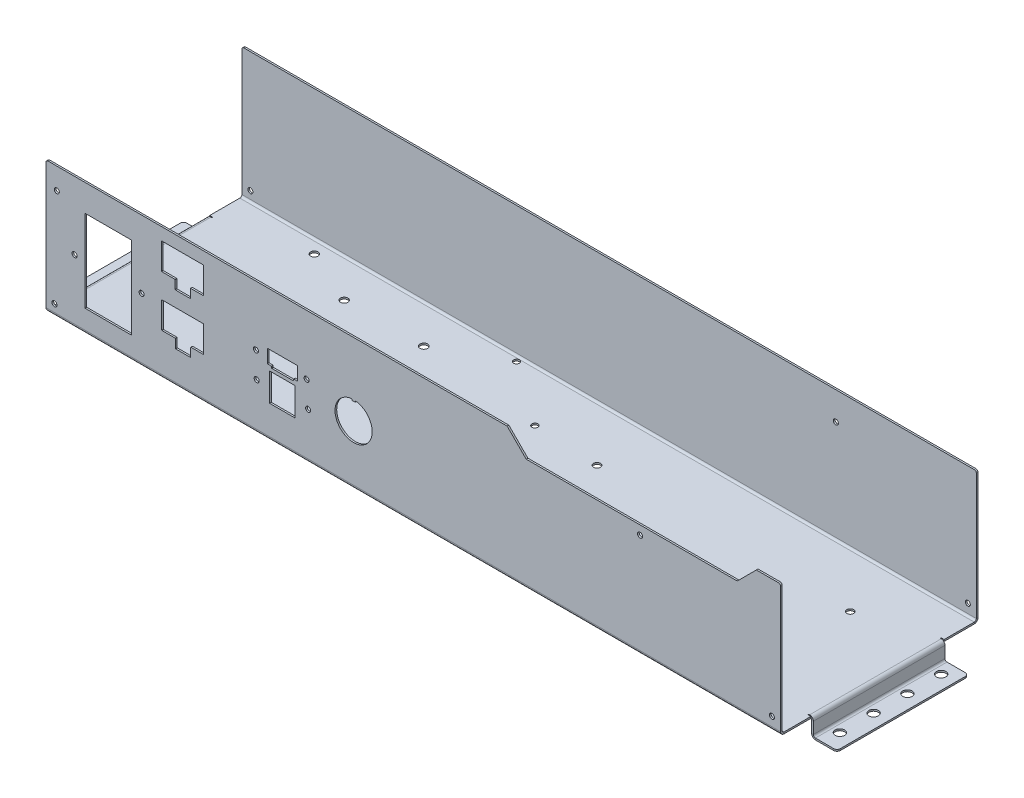
SolidWorks part; units mm, degrees
note: The reader was unsure of these and kept them because the rebuilt part matched: flange length of "Edge-Flange1", "Edge-Flange2", "Edge-Flange3", "Edge-Flange4".
material "1023 Carbon Steel Sheet (SS)"
ref_plane "Front Plane" through (0, 0, 0) normal (0, 0, 1) x (1, 0, 0)
ref_plane "Top Plane" through (0, 0, 0) normal (0, 1, 0) x (1, 0, 0)
ref_plane "Right Plane" through (0, 0, 0) normal (1, 0, 0) x (0, 0, -1)
sketch "Sketch1" plane through (0, 0, 0) normal (0, 1, 0) x (1, 0, 0)
  line L1 (-217.5, -57.5) -> (217.5, -57.5)
  line L2 (-217.5, -57.5) -> (-217.5, 57.5)
  line L3 (-217.5, 57.5) -> (217.5, 57.5)
  line L4 (217.5, -57.5) -> (217.5, 57.5)
  line L5 (-217.5, -57.5) -> (217.5, 57.5) construction
  line L6 (-217.5, 57.5) -> (217.5, -57.5) construction
  point P0 (0, 0)
base flange "Base-Flange1" sketch "Sketch1" thickness 1 reverse thickness direction no parameters "D1"=1.214
edge flange "Edge-Flange1" sketch "Sketch8" flange angle 90 flange length 78 flange position material outside bend radius 1.214 thickness 1 relief rectangular parameters "D6"=10
sketch "Sketch8" plane through (0, 0, 57.5) normal (0, 0, 1) x (1, 0, 0)
  line L0 (-217.5, 0) -> (217.5, 0) construction
  line L1 (-217.5, 0) -> (217.5, 0)
  line L2 (-217.5, 0) -> (-217.5, 77)
  line L3 (-217.5, 77) -> (217.5, 77)
  line L4 (217.5, 77) -> (217.5, 0)
bend "EdgeBend1" bend radius 1.214 bend angle 90 parameters "D5"=1
edge flange "Edge-Flange2" sketch "Sketch11" flange angle 90 flange length 78 flange position material outside bend radius 1.214 thickness 1 relief rectangular parameters "D6"=10
sketch "Sketch11" plane through (0, 0, -57.5) normal (0, 0, -1) x (-1, 0, 0)
  line L0 (-217.5, 0) -> (217.5, 0) construction
  line L1 (-217.5, 0) -> (217.5, 0)
  line L2 (-217.5, 0) -> (-217.5, 77)
  line L3 (-217.5, 77) -> (217.5, 77)
  line L4 (217.5, 77) -> (217.5, 0)
bend "EdgeBend2" bend radius 1.214 bend angle 90 parameters "D5"=2
edge flange "Edge-Flange3" sketch "Sketch35" flange angle 90 flange length 10.214 flange position material outside bend radius 1.214 thickness 1 relief rectangular parameters "D6"=10
bend "EdgeBend5" bend radius 1.214 bend angle 90 parameters "D5"=3
sketch "Sketch35" plane through (217.5, -1, 0) normal (1, 0, 0) x (0, 0, 1)
  line L5 (56.286, 0) -> (-56.286, 0) construction
  line L7 (-37.9399, 0) -> (39.9995, 0)
  line L8 (-37.9399, 0) -> (-37.9399, 9.214)
  line L9 (-37.9399, 9.214) -> (39.9995, 9.214)
  line L10 (39.9995, 0) -> (39.9995, 9.214)
  line L11 (-37.9399, 0) -> (39.9995, 9.214) construction
  line L12 (-37.9399, 9.214) -> (39.9995, 0) construction
  point P8 (1.0298, 4.607)
edge flange "Edge-Flange4" sketch "Sketch39" flange angle 90 flange length 15 flange position material outside bend radius 1.214 thickness 1 relief rectangular parameters "D6"=10
bend "EdgeBend6" bend radius 1.214 bend angle 90 parameters "D5"=4
sketch "Sketch39" plane through (218.5, -10.214, 0) normal (0, -1, 0) x (0, 0, -1)
  line L0 (-39.9995, 0) -> (37.9399, 0) construction
  line L1 (-39.9995, 0) -> (37.9399, 0)
  line L2 (-39.9995, 0) -> (-39.9995, 14)
  line L3 (-39.9995, 14) -> (37.9399, 14)
  line L4 (37.9399, 14) -> (37.9399, 0)
mirror "Mirror1" about plane through (0, 0, 0) normal (1, 0, 0) of "Edge-Flange3", "Edge-Flange4"
bend "MirrorBend3" bend radius 1.214 bend angle 90 parameters "D5"=9
bend "MirrorBend4" bend radius 1.214 bend angle 90 parameters "D5"=12
fillet "Fillet1" radius 2 4 edges at (-232.5, -10.714, 39.9995) (-232.5, -10.714, -37.9399) (232.5, -10.714, -37.9399) (232.5, -10.714, 39.9995)
fillet "Fillet2" radius 1.21 4 edges at (-217.5, 77, 58) (-217.5, 77, -58) (217.5, 77, -58) (217.5, 77, 58)
sketch "Sketch18" plane through (0, 0, 58.5) normal (0, 0, 1) x (1, 0, 0)
  line L1 (216.29, 77) -> (-216.29, 77) construction
  line L4 (191.9151, 65.6863) -> (203.2288, 77)
  line L5 (191.9151, 65.6863) -> (66.9151, 65.6863)
  line L6 (66.9151, 65.6863) -> (55.6014, 77)
  line L7 (55.6014, 77) -> (203.2288, 77)
extrude "Cut-Extrude1" cut sketch "Sketch18" against normal blind 10 normal cut yes
sketch "Sketch23" plane through (0, 0, 58.5) normal (0, 0, 1) x (1, 0, 0)
  line L1 (-92.7472, 26.6535) -> (-77.4972, 26.6535) construction
  line L2 (-85.0472, 18.3535) -> (-69.9472, 18.3535)
  line L3 (-85.0472, 18.3535) -> (-85.0472, 34.9535)
  line L4 (-85.0472, 34.9535) -> (-69.9472, 34.9535)
  line L5 (-69.9472, 18.3535) -> (-69.9472, 34.9535)
  line L6 (-85.0472, 18.3535) -> (-69.9472, 34.9535) construction
  line L7 (-85.0472, 34.9535) -> (-69.9472, 18.3535) construction
  line L8 (-77.4972, 26.6535) -> (-62.2472, 26.6535) construction
  circle A1 centre (-92.7472, 26.6535) radius 1.5
  circle A2 centre (-62.2472, 26.6535) radius 1.5
  point P6 (-77.4972, 26.6535)
extrude "Cut-Extrude3" cut sketch "Sketch23" against normal blind 10 normal cut yes
sketch "Sketch24" plane through (0, 0, 58.5) normal (0, 0, 1) x (1, 0, 0)
  line L5 (-36.1212, 44.2123) -> (-34.5212, 44.2123)
  line L6 (-36.3212, 44.4123) -> (-36.3212, 44.8271)
  line L8 (-34.3212, 44.4123) -> (-34.3212, 44.8271)
  arc A0 (-36.5434, 45.0259) -> (-34.0989, 45.0259) centre (-35.3212, 34.094) ccw
  arc A2 (-34.0989, 45.0259) -> (-34.3212, 44.8271) centre (-34.1212, 44.8271) ccw
  arc A3 (-36.5434, 45.0259) -> (-36.3212, 44.8271) centre (-36.5212, 44.8271) cw
  arc A4 (-34.5212, 44.2123) -> (-34.3212, 44.4123) centre (-34.5212, 44.4123) ccw
  arc A5 (-36.3212, 44.4123) -> (-36.1212, 44.2123) centre (-36.1212, 44.4123) ccw
  dimension "D1" = 0.2
extrude "Cut-Extrude4" cut sketch "Sketch24" against normal blind 10 normal cut yes
sketch "Sketch25" plane through (0, 0, 58.5) normal (0, 0, 1) x (1, 0, 0)
  line L1 (-78.1609, 41.649) -> (-93.1609, 41.649) construction
  line L2 (-86.2439, 45.9317) -> (-68.7439, 45.9317)
  line L3 (-86.4439, 45.7317) -> (-86.4439, 38.1317)
  line L4 (-83.7275, 36.9025) -> (-71.1715, 36.9025)
  line L5 (-68.5439, 45.7317) -> (-68.5439, 38.1317)
  line L6 (-86.4439, 45.9317) -> (-69.8778, 37.3662) construction
  line L7 (-85.0353, 37.3556) -> (-68.5439, 45.9317) construction
  line L8 (-78.1609, 41.649) -> (-63.1609, 41.649) construction
  line L12 (-86.2439, 37.9317) -> (-84.1275, 37.9317)
  line L13 (-83.9275, 37.1025) -> (-83.9275, 37.7317)
  line L14 (-85.0353, 37.3556) -> (-83.9275, 37.9317) construction
  line L15 (-86.4439, 37.9317) -> (-83.9275, 36.9025) construction
  line L18 (-68.7439, 37.9317) -> (-70.7715, 37.9317)
  line L19 (-70.9715, 37.1025) -> (-70.9715, 37.7317)
  line L20 (-69.8778, 37.3662) -> (-70.9715, 37.9317) construction
  line L21 (-68.5439, 37.9317) -> (-70.9715, 36.9025) construction
  circle A0 centre (-93.1609, 41.649) radius 1.5
  circle A1 centre (-63.1609, 41.649) radius 1.5
  arc A2 (-86.4439, 45.7317) -> (-86.2439, 45.9317) centre (-86.2439, 45.7317) cw
  arc A3 (-68.7439, 45.9317) -> (-68.5439, 45.7317) centre (-68.7439, 45.7317) cw
  arc A4 (-86.2439, 37.9317) -> (-86.4439, 38.1317) centre (-86.2439, 38.1317) cw
  arc A5 (-68.5439, 38.1317) -> (-68.7439, 37.9317) centre (-68.7439, 38.1317) cw
  arc A6 (-70.9715, 37.7317) -> (-70.7715, 37.9317) centre (-70.7715, 37.7317) cw
  arc A7 (-70.9715, 37.1025) -> (-71.1715, 36.9025) centre (-71.1715, 37.1025) cw
  arc A8 (-83.9275, 37.1025) -> (-83.7275, 36.9025) centre (-83.7275, 37.1025) ccw
  arc A9 (-84.1275, 37.9317) -> (-83.9275, 37.7317) centre (-84.1275, 37.7317) cw
  point P6 (-77.4681, 41.2908)
  point P15 (-85.0353, 37.3556)
  point P19 (-69.8778, 37.3662)
  dimension "D1" = 0.2
extrude "Cut-Extrude5" cut sketch "Sketch25" against normal blind 10 normal cut yes
sketch "Sketch26" plane through (0, 0, 58.5) normal (0, 0, 1) x (1, 0, 0)
  line L2 (-196.1304, 12.4029) -> (-166.9783, 12.4029) construction
  line L3 (-180.7283, 36.8029) -> (-200.5783, 36.8029) construction
  line L4 (-166.9783, 12.6032) -> (-166.9783, 60.9529)
  line L5 (-167.1787, 12.4032) -> (-194.2787, 12.4526)
  line L6 (-194.4783, 12.6526) -> (-194.4783, 60.9529)
  line L7 (-167.1783, 61.1529) -> (-194.2783, 61.1529)
  line L8 (-166.9783, 12.4029) -> (-194.4783, 61.1529) construction
  line L9 (-194.4783, 12.453) -> (-166.9783, 61.1529) construction
  line L10 (-180.7283, 36.8029) -> (-160.8783, 36.7779) construction
  line L13 (-148.7511, 39.548) -> (-124.3511, 39.548)
  line L16 (-148.9511, 69.6821) -> (-124.5511, 69.6821)
  line L18 (-141.2011, 53.9321) -> (-148.9511, 53.9321)
  line L19 (-140.8011, 48.5821) -> (-132.2011, 48.5821)
  line L25 (-141.0011, 23.798) -> (-148.7511, 23.798)
  line L26 (-149.1511, 69.4821) -> (-149.1511, 54.1321)
  line L32 (-132.0011, 53.7321) -> (-132.0011, 48.7821)
  line L35 (-141.0011, 48.7821) -> (-141.0011, 53.7321)
  line L36 (-131.8011, 53.9321) -> (-124.5511, 53.9321)
  line L37 (-124.3511, 54.1321) -> (-124.3511, 69.4821)
  line L38 (-140.6011, 18.448) -> (-132.0011, 18.448)
  line L39 (-148.9511, 39.348) -> (-148.9511, 23.998)
  line L40 (-131.8011, 23.598) -> (-131.8011, 18.648)
  line L41 (-140.8011, 18.648) -> (-140.8011, 23.598)
  line L42 (-131.6011, 23.798) -> (-124.3511, 23.798)
  line L43 (-124.1511, 23.998) -> (-124.1511, 39.348)
  circle A0 centre (-200.5783, 36.8029) radius 1.5
  circle A1 centre (-160.8783, 36.7779) radius 1.5
  arc A2 (-148.9511, 53.9321) -> (-149.1511, 54.1321) centre (-148.9511, 54.1321) cw
  arc A3 (-141.2011, 53.9321) -> (-141.0011, 53.7321) centre (-141.2011, 53.7321) cw
  arc A4 (-140.8011, 48.5821) -> (-141.0011, 48.7821) centre (-140.8011, 48.7821) cw
  arc A5 (-132.0011, 48.7821) -> (-132.2011, 48.5821) centre (-132.2011, 48.7821) cw
  arc A6 (-132.0011, 53.7321) -> (-131.8011, 53.9321) centre (-131.8011, 53.7321) cw
  arc A7 (-124.5511, 53.9321) -> (-124.3511, 54.1321) centre (-124.5511, 54.1321) ccw
  arc A8 (-124.5511, 69.6821) -> (-124.3511, 69.4821) centre (-124.5511, 69.4821) cw
  arc A9 (-149.1511, 69.4821) -> (-148.9511, 69.6821) centre (-148.9511, 69.4821) cw
  arc A10 (-148.7511, 23.798) -> (-148.9511, 23.998) centre (-148.7511, 23.998) cw
  arc A11 (-141.0011, 23.798) -> (-140.8011, 23.598) centre (-141.0011, 23.598) cw
  arc A12 (-140.6011, 18.448) -> (-140.8011, 18.648) centre (-140.6011, 18.648) cw
  arc A13 (-131.8011, 18.648) -> (-132.0011, 18.448) centre (-132.0011, 18.648) cw
  arc A14 (-131.8011, 23.598) -> (-131.6011, 23.798) centre (-131.6011, 23.598) cw
  arc A15 (-124.3511, 23.798) -> (-124.1511, 23.998) centre (-124.3511, 23.998) ccw
  arc A16 (-124.3511, 39.548) -> (-124.1511, 39.348) centre (-124.3511, 39.348) cw
  arc A17 (-148.9511, 39.348) -> (-148.7511, 39.548) centre (-148.7511, 39.348) cw
  arc A18 (-166.9783, 60.9529) -> (-167.1783, 61.1529) centre (-167.1783, 60.9529) ccw
  arc A19 (-167.1787, 12.4032) -> (-166.9783, 12.6032) centre (-167.1783, 12.6032) ccw
  arc A20 (-194.2787, 12.4526) -> (-194.4783, 12.6526) centre (-194.2783, 12.6526) cw
  arc A21 (-194.4783, 60.9529) -> (-194.2783, 61.1529) centre (-194.2783, 60.9529) cw
  point P8 (-180.7354, 36.7904)
  point P25 (-136.5011, 51.2571)
  point P51 (-103.5793, 43.7286)
  dimension "D1" = 0.2
  dimension "D3" = 0.2
extrude "Cut-Extrude6" cut sketch "Sketch26" against normal blind 10 normal cut yes
sketch "Sketch28" plane through (0, 0, 58.5) normal (0, 0, 1) x (1, 0, 0)
  line L3 (-66.8168, 56.388) -> (-87.3168, 56.388)
  line L4 (-66.6168, 56.188) -> (-66.6168, 51.088)
  line L6 (-87.5168, 56.188) -> (-87.5168, 51.088)
  line L8 (-75.0865, 50.888) -> (-66.8168, 50.888)
  line L9 (-77.0668, 49.188) -> (-75.0865, 49.188) construction
  line L10 (-77.0668, 49.188) -> (-79.0471, 49.188) construction
  line L12 (-75.0865, 49.188) -> (-79.0471, 49.188)
  line L13 (-75.0865, 49.188) -> (-75.0865, 50.888)
  line L15 (-79.0471, 49.188) -> (-79.0471, 50.888)
  line L16 (-79.0471, 50.888) -> (-87.3168, 50.888)
  arc A0 (-87.3168, 50.888) -> (-87.5168, 51.088) centre (-87.3168, 51.088) cw
  arc A1 (-87.3168, 56.388) -> (-87.5168, 56.188) centre (-87.3168, 56.188) ccw
  arc A2 (-66.8168, 56.388) -> (-66.6168, 56.188) centre (-66.8168, 56.188) cw
  arc A3 (-66.6168, 51.088) -> (-66.8168, 50.888) centre (-66.8168, 51.088) cw
  point P6 (-77.0668, 56.388)
  dimension "D2" = 0.2
sketch "Sketch29" plane through (0, -1, 0) normal (0, -1, 0) x (1, 0, 0)
  line L5 (-216.286, 56.286) -> (-216.286, -56.286) construction
  line L6 (-216.286, 56.286) -> (206.646, 56.286) construction
  line L7 (206.646, 56.286) -> (206.646, -56.286) construction
  line L8 (-216.286, -56.286) -> (206.646, -56.286) construction
  line L9 (-216.286, 56.286) -> (206.646, -56.286) construction
  line L10 (206.646, 56.286) -> (-216.286, -56.286) construction
  circle A0 centre (-166.7317, -2.49) radius 2.2
  circle A1 centre (-166.7317, -49.66) radius 2.2
  circle A2 centre (-134.2117, -34.82) radius 2.2
  circle A3 centre (-87.0417, -34.82) radius 2.2731
  circle A4 centre (-95.9046, 5) radius 1.8481
  circle A5 centre (-37.9046, 5) radius 1.85
  circle A6 centre (-37.9046, 54) radius 1.85
  circle A9 centre (-51.698, -54.38) radius 1.75
  circle A11 centre (-13.438, -27.02) radius 1.786
  circle A12 centre (25.36, -25) radius 2.0474
  circle A13 centre (25.36, 25) radius 2
  circle A14 centre (175.36, 25) radius 2
  circle A15 centre (175.36, -25) radius 2
  point P52 (-4.213, -0.607)
  point P57 (-4.82, 0)
extrude "Cut-Extrude8" cut sketch "Sketch29" against normal blind 10 normal cut yes
sketch "Sketch30" plane through (0, 0, 58.5) normal (0, 0, 1) x (1, 0, 0)
  line L0 (-212.3259, 76.6451) -> (212.6797, 76.6451) construction
  line L1 (-212.3259, 76.6451) -> (-212.3259, 1.2135) construction
  line L2 (-212.3259, 1.2135) -> (212.6797, 1.2135) construction
  line L3 (212.6797, 76.6451) -> (212.6797, 1.2135) construction
  line L4 (-212.3259, 76.6451) -> (212.6797, 1.2135) construction
  line L5 (-212.3259, 1.2135) -> (212.6797, 76.6451) construction
  circle A0 centre (212.4742, 6.5618) radius 1.5
  circle A1 centre (134.3351, 60.4505) radius 1.5
  circle A2 centre (-212.4748, 5.6818) radius 1.5
  point P4 (0.1769, 38.9293)
extrude "Cut-Extrude9" cut sketch "Sketch30" against normal blind 10 normal cut yes
mirror "Mirror2" about plane through (0, 0, 0) normal (0, 0, 1) of "Cut-Extrude9"
sketch "Sketch31" plane through (0, -10.214, 0) normal (0, 1, 0) x (1, 0, 0)
  line L0 (-232.5, 0) -> (-224.18, 0) construction
  line L2 (-224.18, 0) -> (-224.18, 10) construction
  circle A0 centre (-224.18, 10) radius 2.8
  circle A1 centre (-224.18, 30) radius 2.8
  dimension "D1" = 2
extrude "Cut-Extrude10" cut sketch "Sketch31" against normal blind 10 normal cut yes
mirror "Mirror3" about plane through (0, 0, 0) normal (0, 0, 1) of "Cut-Extrude10"
mirror "Mirror4" about plane through (0, 0, 0) normal (1, 0, 0) of "Mirror3", "Cut-Extrude10"
sketch "Sketch37" plane through (0, 0, 58.5) normal (0, 0, 1) x (1, 0, 0)
  line L0 (-217.1456, 76.6456) -> (-217.1456, 64.3256) construction
  line L1 (-217.1456, 64.3256) -> (-211.1156, 64.3256) construction
  arc A0 (-216.29, 77) -> (-217.5, 75.79) centre (-216.29, 75.79) ccw construction
  circle A1 centre (-211.1156, 64.3256) radius 1.5
extrude "Cut-Extrude12" cut sketch "Sketch37" against normal blind 10 normal cut yes
sketch "Bend-Lines1" [suppressed] plane through (0, 0, 0) normal (0, 1, 0) x (1, 0, 0)
sketch "Bounding-Box1" [suppressed] plane through (0, 0, 0) normal (0, 1, 0) x (1, 0, 0)
sheet metal parameters "Sheet-Metal1" thickness 1 parameters "D1"=1.214
flat pattern "Flat-Pattern1" [suppressed]
sketch "Bend-Lines2" plane through (0, 0, 0) normal (0, 1, 0) x (1, 0, 0)
sketch3d "Bounding-Box2" [suppressed]
  line L0 (-212.68, 57.5, 0) -> (212.68, 57.5, 0) construction
  line L1 (-212.68, -57.5, 0) -> (212.68, -57.5, 0) construction
  line L2 (-212.68, 57.5, 0) -> (-212.68, -57.5, 0) construction
  line L3 (212.68, 57.5, 0) -> (212.68, -57.5, 0) construction
sheet metal parameters "Sheet-Metal2" thickness 1 parameters "D1"=1.214
flat pattern "Flat-Pattern1"
sketch "Bend-Lines2" plane through (0, 0, 0) normal (0, 1, 0) x (1, 0, 0)
  line L0 (-212.68, -57.6322) -> (212.68, -57.6322) construction
  line L1 (-212.68, -57.6322) -> (212.68, -57.6322) construction
sketch3d "Bounding-Box2" [suppressed]
  line L0 (212.68, 57.5, 0) -> (-212.68, 57.5, 0) construction
  line L1 (212.68, -134.7643, 0) -> (-212.68, -134.7643, 0) construction
  line L2 (212.68, 57.5, 0) -> (212.68, -134.7643, 0) construction
  line L3 (-212.68, 57.5, 0) -> (-212.68, -134.7643, 0) construction
bend of the flat pattern "Flatten-<EdgeBend1>1"
sheet metal parameters "Sheet-Metal3" thickness 1 parameters "D1"=1.214
flat pattern "Flat-Pattern1"
sketch "Bend-Lines2" plane through (0, 0, 0) normal (0, 1, 0) x (1, 0, 0)
  line L0 (-212.68, -57.6322) -> (212.68, -57.6322) construction
  line L1 (-212.68, -57.6322) -> (212.68, -57.6322) construction
  line L2 (212.68, 57.6322) -> (-212.68, 57.6322) construction
  line L3 (212.68, 57.6322) -> (-212.68, 57.6322) construction
sketch3d "Bounding-Box2" [suppressed]
  line L0 (212.68, 134.7643, 0) -> (-212.68, 134.7643, 0) construction
  line L1 (212.68, -134.7643, 0) -> (-212.68, -134.7643, 0) construction
  line L2 (212.68, 134.7643, 0) -> (212.68, -134.7643, 0) construction
  line L3 (-212.68, 134.7643, 0) -> (-212.68, -134.7643, 0) construction
bend of the flat pattern "Flatten-<EdgeBend1>1"
bend of the flat pattern "Flatten-<EdgeBend2>1"
sheet metal parameters "Sheet-Metal4" thickness 1 parameters "D1"=1.214
flat pattern "Flat-Pattern1" [suppressed]
sketch "Bend-Lines2" plane through (0, -1, 0) normal (0, -1, 0) x (-1, 0, 0)
  line L0 (217.5, -57.6322) -> (-217.5, -57.6322) construction
  line L1 (217.5, -57.6322) -> (-217.5, -57.6322) construction
  line L2 (-217.5, 57.6322) -> (217.5, 57.6322) construction
  line L3 (-217.5, 57.6322) -> (217.5, 57.6322) construction
  line L6 (-217.6322, -39.9995) -> (-217.6322, 37.9399) construction
  line L7 (-217.6322, -39.9995) -> (-217.6322, 37.9399) construction
  point P4 (217.6322, -45)
  point P5 (217.6322, 22.5)
sketch3d "Bounding-Box2" [suppressed]
  line L0 (-226.9783, 134.7643, 0) -> (217.5, 134.7643, 0) construction
  line L1 (-226.9783, -134.7643, 0) -> (217.5, -134.7643, 0) construction
  line L2 (-226.9783, 134.7643, 0) -> (-226.9783, -134.7643, 0) construction
  line L3 (217.5, 134.7643, 0) -> (217.5, -134.7643, 0) construction
bend of the flat pattern "Flatten-<EdgeBend1>1"
bend of the flat pattern "Flatten-<EdgeBend2>1"
bend of the flat pattern "Flatten-<EdgeBend5>1"
sketch "Sketch28-2" plane through (0, -1, 57.7643) normal (0, -1, 0) x (1, 0, 0)
  line L3 (-66.8168, 56.388) -> (-87.3168, 56.388)
  line L4 (-66.6168, 56.188) -> (-66.6168, 51.088)
  line L6 (-87.5168, 56.188) -> (-87.5168, 51.088)
  line L8 (-75.0865, 50.888) -> (-66.8168, 50.888)
  line L9 (-77.0668, 49.188) -> (-75.0865, 49.188) construction
  line L10 (-77.0668, 49.188) -> (-79.0471, 49.188) construction
  line L12 (-75.0865, 49.188) -> (-79.0471, 49.188)
  line L13 (-75.0865, 49.188) -> (-75.0865, 50.888)
  line L15 (-79.0471, 49.188) -> (-79.0471, 50.888)
  line L16 (-79.0471, 50.888) -> (-87.3168, 50.888)
  arc A0 (-87.3168, 50.888) -> (-87.5168, 51.088) centre (-87.3168, 51.088) cw
  arc A1 (-87.3168, 56.388) -> (-87.5168, 56.188) centre (-87.3168, 56.188) ccw
  arc A2 (-66.8168, 56.388) -> (-66.6168, 56.188) centre (-66.8168, 56.188) cw
  arc A3 (-66.6168, 51.088) -> (-66.8168, 50.888) centre (-66.8168, 51.088) cw
  dimension "D2" = 0.2
sheet metal parameters "Sheet-Metal5" thickness 1 parameters "D1"=1.214
flat pattern "Flat-Pattern1" [suppressed]
sketch "Bend-Lines2" plane through (0, 0, 0) normal (0, 1, 0) x (1, 0, 0)
  line L0 (-212.68, -57.6322) -> (212.68, -57.6322) construction
  line L1 (-212.68, -57.6322) -> (212.68, -57.6322) construction
  line L2 (212.68, 57.6322) -> (-212.68, 57.6322) construction
  line L3 (212.68, 57.6322) -> (-212.68, 57.6322) construction
  line L4 (212.8122, -56.286) -> (212.8122, 56.286) construction
  line L5 (212.8122, -56.286) -> (212.8122, 56.286) construction
  line L6 (222.2905, -56.286) -> (222.2905, 56.286) construction
  line L7 (222.2905, -56.286) -> (222.2905, 56.286) construction
sketch3d "Bounding-Box2" [suppressed]
  line L0 (241.4227, 134.7643, 0) -> (-212.68, 134.7643, 0) construction
  line L1 (241.4227, -134.7643, 0) -> (-212.68, -134.7643, 0) construction
  line L2 (241.4227, 134.7643, 0) -> (241.4227, -134.7643, 0) construction
  line L3 (-212.68, 134.7643, 0) -> (-212.68, -134.7643, 0) construction
bend of the flat pattern "Flatten-<EdgeBend1>1"
bend of the flat pattern "Flatten-<EdgeBend2>1"
bend of the flat pattern "Flatten-<EdgeBend5>2"
bend of the flat pattern "Flatten-<EdgeBend6>1"
sheet metal parameters "Sheet-Metal6" thickness 1 parameters "D1"=1.214
flat pattern "Flat-Pattern1" [suppressed]
sketch "Bend-Lines2" plane through (0, 0, 0) normal (0, 1, 0) x (1, 0, 0)
  line L0 (-212.68, -57.6322) -> (212.68, -57.6322) construction
  line L1 (-212.68, -57.6322) -> (212.68, -57.6322) construction
  line L2 (212.68, 57.6322) -> (-212.68, 57.6322) construction
  line L3 (212.68, 57.6322) -> (-212.68, 57.6322) construction
  line L4 (212.8122, -56.286) -> (212.8122, 56.286) construction
  line L5 (212.8122, -56.286) -> (212.8122, 56.286) construction
  line L6 (222.2905, -56.286) -> (222.2905, 56.286) construction
  line L7 (222.2905, -56.286) -> (222.2905, 56.286) construction
  line L8 (-222.2905, 56.286) -> (-222.2905, -56.286) construction
  line L9 (-212.8122, 56.286) -> (-212.8122, -56.286) construction
  line L10 (-222.2905, 56.286) -> (-222.2905, -56.286) construction
  line L11 (-212.8122, 56.286) -> (-212.8122, -56.286) construction
sketch3d "Bounding-Box2" [suppressed]
  line L0 (241.4227, 134.7643, 0) -> (-241.4227, 134.7643, 0) construction
  line L1 (241.4227, -134.7643, 0) -> (-241.4227, -134.7643, 0) construction
  line L2 (241.4227, 134.7643, 0) -> (241.4227, -134.7643, 0) construction
  line L3 (-241.4227, 134.7643, 0) -> (-241.4227, -134.7643, 0) construction
bend of the flat pattern "Flatten-<EdgeBend1>1"
bend of the flat pattern "Flatten-<EdgeBend2>1"
bend of the flat pattern "Flatten-<EdgeBend5>3"
bend of the flat pattern "Flatten-<MirrorBend3>1"
bend of the flat pattern "Flatten-<EdgeBend6>2"
bend of the flat pattern "Flatten-<MirrorBend4>1"
sheet metal parameters "Sheet-Metal7" thickness 1 parameters "D1"=1.214
flat pattern "Flat-Pattern1" [suppressed]
sketch "Bend-Lines2" plane through (0, 0, 0) normal (0, 1, 0) x (1, 0, 0)
  line L0 (-212.68, -57.6322) -> (212.68, -57.6322) construction
  line L1 (-212.68, -57.6322) -> (212.68, -57.6322) construction
  line L2 (212.68, 57.6322) -> (-212.68, 57.6322) construction
  line L3 (212.68, 57.6322) -> (-212.68, 57.6322) construction
  line L4 (212.8122, -56.286) -> (212.8122, 56.286) construction
  line L5 (212.8122, -56.286) -> (212.8122, 56.286) construction
  line L6 (222.2905, -56.286) -> (222.2905, 56.286) construction
  line L7 (222.2905, -56.286) -> (222.2905, 56.286) construction
  line L8 (-222.2905, 56.286) -> (-222.2905, -56.286) construction
  line L9 (-212.8122, 56.286) -> (-212.8122, -56.286) construction
  line L10 (-222.2905, 56.286) -> (-222.2905, -56.286) construction
  line L11 (-212.8122, 56.286) -> (-212.8122, -56.286) construction
sketch3d "Bounding-Box2" [suppressed]
  line L0 (241.4227, 134.7643, 0) -> (-241.4227, 134.7643, 0) construction
  line L1 (241.4227, -134.7643, 0) -> (-241.4227, -134.7643, 0) construction
  line L2 (241.4227, 134.7643, 0) -> (241.4227, -134.7643, 0) construction
  line L3 (-241.4227, 134.7643, 0) -> (-241.4227, -134.7643, 0) construction
bend of the flat pattern "Flatten-<EdgeBend1>1"
bend of the flat pattern "Flatten-<EdgeBend2>1"
bend of the flat pattern "Flatten-<EdgeBend5>4"
bend of the flat pattern "Flatten-<MirrorBend3>2"
bend of the flat pattern "Flatten-<EdgeBend6>3"
bend of the flat pattern "Flatten-<MirrorBend4>2"
sheet metal parameters "Sheet-Metal9" thickness 1 parameters "D1"=1.214
flat pattern "Flat-Pattern1" [suppressed]
sketch "Bend-Lines2" plane through (0, 0, 0) normal (0, 1, 0) x (1, 0, 0)
  line L0 (-212.68, -57.6322) -> (212.68, -57.6322) construction
  line L1 (-212.68, -57.6322) -> (212.68, -57.6322) construction
  line L2 (212.68, 57.6322) -> (-212.68, 57.6322) construction
  line L3 (212.68, 57.6322) -> (-212.68, 57.6322) construction
  line L4 (212.8122, -56.286) -> (212.8122, 56.286) construction
  line L5 (212.8122, -56.286) -> (212.8122, 56.286) construction
  line L6 (222.2905, -56.286) -> (222.2905, 56.286) construction
  line L7 (222.2905, -56.286) -> (222.2905, 56.286) construction
  line L8 (-222.2905, 56.286) -> (-222.2905, -56.286) construction
  line L9 (-212.8122, 56.286) -> (-212.8122, -56.286) construction
  line L10 (-222.2905, 56.286) -> (-222.2905, -56.286) construction
  line L11 (-212.8122, 56.286) -> (-212.8122, -56.286) construction
sketch3d "Bounding-Box2" [suppressed]
  line L0 (241.4227, 134.7643, 0) -> (-241.4227, 134.7643, 0) construction
  line L1 (241.4227, -134.7643, 0) -> (-241.4227, -134.7643, 0) construction
  line L2 (241.4227, 134.7643, 0) -> (241.4227, -134.7643, 0) construction
  line L3 (-241.4227, 134.7643, 0) -> (-241.4227, -134.7643, 0) construction
bend of the flat pattern "Flatten-<EdgeBend1>1"
bend of the flat pattern "Flatten-<EdgeBend2>1"
bend of the flat pattern "Flatten-<EdgeBend5>5"
bend of the flat pattern "Flatten-<MirrorBend3>3"
bend of the flat pattern "Flatten-<EdgeBend6>4"
bend of the flat pattern "Flatten-<MirrorBend4>3"
sheet metal parameters "Sheet-Metal10" thickness 1 parameters "D1"=1.214
flat pattern "Flat-Pattern1" [suppressed]
sketch "Bend-Lines2" plane through (0, 0, 0) normal (0, 1, 0) x (1, 0, 0)
  line L0 (-212.68, -57.6322) -> (212.68, -57.6322) construction
  line L1 (-212.68, -57.6322) -> (212.68, -57.6322) construction
  line L2 (212.68, 57.6322) -> (-212.68, 57.6322) construction
  line L3 (212.68, 57.6322) -> (-212.68, 57.6322) construction
  line L4 (212.8122, -56.286) -> (212.8122, 56.286) construction
  line L5 (212.8122, -56.286) -> (212.8122, 56.286) construction
  line L6 (222.2905, -56.286) -> (222.2905, 56.286) construction
  line L7 (222.2905, -56.286) -> (222.2905, 56.286) construction
  line L8 (-222.2905, 56.286) -> (-222.2905, -56.286) construction
  line L9 (-212.8122, 56.286) -> (-212.8122, -56.286) construction
  line L10 (-222.2905, 56.286) -> (-222.2905, -56.286) construction
  line L11 (-212.8122, 56.286) -> (-212.8122, -56.286) construction
sketch3d "Bounding-Box2" [suppressed]
  line L0 (241.4227, 134.7643, 0) -> (-241.4227, 134.7643, 0) construction
  line L1 (241.4227, -134.7643, 0) -> (-241.4227, -134.7643, 0) construction
  line L2 (241.4227, 134.7643, 0) -> (241.4227, -134.7643, 0) construction
  line L3 (-241.4227, 134.7643, 0) -> (-241.4227, -134.7643, 0) construction
bend of the flat pattern "Flatten-<EdgeBend1>1"
bend of the flat pattern "Flatten-<EdgeBend2>1"
bend of the flat pattern "Flatten-<EdgeBend5>6"
bend of the flat pattern "Flatten-<MirrorBend3>4"
bend of the flat pattern "Flatten-<EdgeBend6>5"
bend of the flat pattern "Flatten-<MirrorBend4>4"
sheet metal parameters "Sheet-Metal11" thickness 1 parameters "D1"=1.214
flat pattern "Flat-Pattern1" [suppressed]
sketch "Bend-Lines2" plane through (0, 0, 0) normal (0, 1, 0) x (1, 0, 0)
  line L0 (-212.68, -57.6322) -> (212.68, -57.6322) construction
  line L1 (-212.68, -57.6322) -> (212.68, -57.6322) construction
  line L2 (212.68, 57.6322) -> (-212.68, 57.6322) construction
  line L3 (212.68, 57.6322) -> (-212.68, 57.6322) construction
  line L4 (212.8122, -56.286) -> (212.8122, 56.286) construction
  line L5 (212.8122, -56.286) -> (212.8122, 56.286) construction
  line L6 (222.2905, -56.286) -> (222.2905, 56.286) construction
  line L7 (222.2905, -56.286) -> (222.2905, 56.286) construction
  line L8 (-222.2905, 56.286) -> (-222.2905, -56.286) construction
  line L9 (-212.8122, 56.286) -> (-212.8122, -56.286) construction
  line L10 (-222.2905, 56.286) -> (-222.2905, -56.286) construction
  line L11 (-212.8122, 56.286) -> (-212.8122, -56.286) construction
sketch3d "Bounding-Box2" [suppressed]
  line L0 (241.4227, 134.7643, 0) -> (-241.4227, 134.7643, 0) construction
  line L1 (241.4227, -134.7643, 0) -> (-241.4227, -134.7643, 0) construction
  line L2 (241.4227, 134.7643, 0) -> (241.4227, -134.7643, 0) construction
  line L3 (-241.4227, 134.7643, 0) -> (-241.4227, -134.7643, 0) construction
bend of the flat pattern "Flatten-<EdgeBend1>1"
bend of the flat pattern "Flatten-<EdgeBend2>1"
bend of the flat pattern "Flatten-<EdgeBend5>7"
bend of the flat pattern "Flatten-<MirrorBend3>5"
bend of the flat pattern "Flatten-<EdgeBend6>6"
bend of the flat pattern "Flatten-<MirrorBend4>5"
sheet metal parameters "Sheet-Metal12" thickness 1 parameters "D1"=1.214
flat pattern "Flat-Pattern1" [suppressed]
sketch "Bend-Lines2" plane through (0, 0, 0) normal (0, 1, 0) x (1, 0, 0)
  line L0 (-212.68, -57.6322) -> (212.68, -57.6322) construction
  line L1 (-212.68, -57.6322) -> (212.68, -57.6322) construction
  line L2 (212.68, 57.6322) -> (-212.68, 57.6322) construction
  line L3 (212.68, 57.6322) -> (-212.68, 57.6322) construction
  line L4 (212.8122, -56.286) -> (212.8122, 56.286) construction
  line L5 (212.8122, -56.286) -> (212.8122, 56.286) construction
  line L6 (222.2905, -56.286) -> (222.2905, 56.286) construction
  line L7 (222.2905, -56.286) -> (222.2905, 56.286) construction
  line L8 (-222.2905, 56.286) -> (-222.2905, -56.286) construction
  line L9 (-212.8122, 56.286) -> (-212.8122, -56.286) construction
  line L10 (-222.2905, 56.286) -> (-222.2905, -56.286) construction
  line L11 (-212.8122, 56.286) -> (-212.8122, -56.286) construction
sketch3d "Bounding-Box2" [suppressed]
  line L0 (241.4227, 134.7643, 0) -> (-241.4227, 134.7643, 0) construction
  line L1 (241.4227, -134.7643, 0) -> (-241.4227, -134.7643, 0) construction
  line L2 (241.4227, 134.7643, 0) -> (241.4227, -134.7643, 0) construction
  line L3 (-241.4227, 134.7643, 0) -> (-241.4227, -134.7643, 0) construction
bend of the flat pattern "Flatten-<EdgeBend1>1"
bend of the flat pattern "Flatten-<EdgeBend2>1"
bend of the flat pattern "Flatten-<EdgeBend5>8"
bend of the flat pattern "Flatten-<MirrorBend3>6"
bend of the flat pattern "Flatten-<EdgeBend6>7"
bend of the flat pattern "Flatten-<MirrorBend4>6"
sheet metal parameters "Sheet-Metal14" thickness 1 parameters "D1"=1.214
flat pattern "Flat-Pattern1" [suppressed]
sketch "Bend-Lines2" plane through (0, 0, 0) normal (0, 1, 0) x (1, 0, 0)
  line L0 (-212.68, -57.6322) -> (212.68, -57.6322) construction
  line L1 (-212.68, -57.6322) -> (212.68, -57.6322) construction
  line L2 (212.68, 57.6322) -> (-212.68, 57.6322) construction
  line L3 (212.68, 57.6322) -> (-212.68, 57.6322) construction
  line L4 (212.8122, -56.286) -> (212.8122, 56.286) construction
  line L5 (212.8122, -56.286) -> (212.8122, 56.286) construction
  line L6 (222.2905, -56.286) -> (222.2905, 56.286) construction
  line L7 (222.2905, -56.286) -> (222.2905, 56.286) construction
  line L8 (-222.2905, 56.286) -> (-222.2905, -56.286) construction
  line L9 (-212.8122, 56.286) -> (-212.8122, -56.286) construction
  line L10 (-222.2905, 56.286) -> (-222.2905, -56.286) construction
  line L11 (-212.8122, 56.286) -> (-212.8122, -56.286) construction
sketch3d "Bounding-Box2" [suppressed]
  line L0 (241.4227, 134.7643, 0) -> (-241.4227, 134.7643, 0) construction
  line L1 (241.4227, -134.7643, 0) -> (-241.4227, -134.7643, 0) construction
  line L2 (241.4227, 134.7643, 0) -> (241.4227, -134.7643, 0) construction
  line L3 (-241.4227, 134.7643, 0) -> (-241.4227, -134.7643, 0) construction
bend of the flat pattern "Flatten-<EdgeBend1>1"
bend of the flat pattern "Flatten-<EdgeBend2>1"
bend of the flat pattern "Flatten-<EdgeBend5>9"
bend of the flat pattern "Flatten-<MirrorBend3>7"
bend of the flat pattern "Flatten-<EdgeBend6>8"
bend of the flat pattern "Flatten-<MirrorBend4>7"
sheet metal parameters "Sheet-Metal15" thickness 1 parameters "D1"=1.214
flat pattern "Flat-Pattern1" [suppressed]
sketch "Bend-Lines2" plane through (0, 0, 0) normal (0, 1, 0) x (1, 0, 0)
  line L0 (-212.68, -57.6322) -> (212.68, -57.6322) construction
  line L1 (-212.68, -57.6322) -> (212.68, -57.6322) construction
  line L2 (212.68, 57.6322) -> (-212.68, 57.6322) construction
  line L3 (212.68, 57.6322) -> (-212.68, 57.6322) construction
  line L4 (212.8122, -56.286) -> (212.8122, 56.286) construction
  line L5 (212.8122, -56.286) -> (212.8122, 56.286) construction
  line L6 (222.2905, -56.286) -> (222.2905, 56.286) construction
  line L7 (222.2905, -56.286) -> (222.2905, 56.286) construction
  line L8 (-222.2905, 56.286) -> (-222.2905, -56.286) construction
  line L9 (-212.8122, 56.286) -> (-212.8122, -56.286) construction
  line L10 (-222.2905, 56.286) -> (-222.2905, -56.286) construction
  line L11 (-212.8122, 56.286) -> (-212.8122, -56.286) construction
sketch3d "Bounding-Box2" [suppressed]
  line L0 (241.4227, 134.7643, 0) -> (-241.4227, 134.7643, 0) construction
  line L1 (241.4227, -134.7643, 0) -> (-241.4227, -134.7643, 0) construction
  line L2 (241.4227, 134.7643, 0) -> (241.4227, -134.7643, 0) construction
  line L3 (-241.4227, 134.7643, 0) -> (-241.4227, -134.7643, 0) construction
bend of the flat pattern "Flatten-<EdgeBend1>1"
bend of the flat pattern "Flatten-<EdgeBend2>1"
bend of the flat pattern "Flatten-<EdgeBend5>10"
bend of the flat pattern "Flatten-<MirrorBend3>8"
bend of the flat pattern "Flatten-<EdgeBend6>9"
bend of the flat pattern "Flatten-<MirrorBend4>8"
sheet metal parameters "Sheet-Metal16" thickness 1 parameters "D1"=1.214
flat pattern "Flat-Pattern1" [suppressed]
sketch "Bend-Lines2" plane through (0, 0, 0) normal (0, 1, 0) x (1, 0, 0)
  line L0 (-212.68, -57.6322) -> (212.68, -57.6322) construction
  line L1 (-212.68, -57.6322) -> (212.68, -57.6322) construction
  line L2 (212.68, 57.6322) -> (-212.68, 57.6322) construction
  line L3 (212.68, 57.6322) -> (-212.68, 57.6322) construction
  line L4 (212.8122, -56.286) -> (212.8122, 56.286) construction
  line L5 (212.8122, -56.286) -> (212.8122, 56.286) construction
  line L6 (222.2905, -56.286) -> (222.2905, 56.286) construction
  line L7 (222.2905, -56.286) -> (222.2905, 56.286) construction
  line L8 (-222.2905, 56.286) -> (-222.2905, -56.286) construction
  line L9 (-212.8122, 56.286) -> (-212.8122, -56.286) construction
  line L10 (-222.2905, 56.286) -> (-222.2905, -56.286) construction
  line L11 (-212.8122, 56.286) -> (-212.8122, -56.286) construction
sketch3d "Bounding-Box2" [suppressed]
  line L0 (241.4227, 134.7643, 0) -> (-241.4227, 134.7643, 0) construction
  line L1 (241.4227, -134.7643, 0) -> (-241.4227, -134.7643, 0) construction
  line L2 (241.4227, 134.7643, 0) -> (241.4227, -134.7643, 0) construction
  line L3 (-241.4227, 134.7643, 0) -> (-241.4227, -134.7643, 0) construction
bend of the flat pattern "Flatten-<EdgeBend1>1"
bend of the flat pattern "Flatten-<EdgeBend2>1"
bend of the flat pattern "Flatten-<EdgeBend5>11"
bend of the flat pattern "Flatten-<MirrorBend3>9"
bend of the flat pattern "Flatten-<EdgeBend6>10"
bend of the flat pattern "Flatten-<MirrorBend4>9"
sheet metal parameters "Sheet-Metal17" thickness 1 parameters "D1"=1.214
flat pattern "Flat-Pattern1" [suppressed]
sketch "Bend-Lines2" plane through (0, 0, 0) normal (0, 1, 0) x (1, 0, 0)
  line L0 (-212.68, -57.6322) -> (212.68, -57.6322) construction
  line L1 (-212.68, -57.6322) -> (212.68, -57.6322) construction
  line L2 (212.68, 57.6322) -> (-212.68, 57.6322) construction
  line L3 (212.68, 57.6322) -> (-212.68, 57.6322) construction
  line L4 (212.8122, -56.286) -> (212.8122, 56.286) construction
  line L5 (212.8122, -56.286) -> (212.8122, 56.286) construction
  line L6 (222.2905, -56.286) -> (222.2905, 56.286) construction
  line L7 (222.2905, -56.286) -> (222.2905, 56.286) construction
  line L8 (-222.2905, 56.286) -> (-222.2905, -56.286) construction
  line L9 (-212.8122, 56.286) -> (-212.8122, -56.286) construction
  line L10 (-222.2905, 56.286) -> (-222.2905, -56.286) construction
  line L11 (-212.8122, 56.286) -> (-212.8122, -56.286) construction
sketch3d "Bounding-Box2" [suppressed]
  line L0 (241.4227, 134.7643, 0) -> (-241.4227, 134.7643, 0) construction
  line L1 (241.4227, -134.7643, 0) -> (-241.4227, -134.7643, 0) construction
  line L2 (241.4227, 134.7643, 0) -> (241.4227, -134.7643, 0) construction
  line L3 (-241.4227, 134.7643, 0) -> (-241.4227, -134.7643, 0) construction
bend of the flat pattern "Flatten-<EdgeBend1>1"
bend of the flat pattern "Flatten-<EdgeBend2>1"
bend of the flat pattern "Flatten-<EdgeBend5>12"
bend of the flat pattern "Flatten-<MirrorBend3>10"
bend of the flat pattern "Flatten-<EdgeBend6>11"
bend of the flat pattern "Flatten-<MirrorBend4>10"
sheet metal parameters "Sheet-Metal18" thickness 1 parameters "D1"=1.214
flat pattern "Flat-Pattern1" [suppressed]
sketch "Bend-Lines2" plane through (0, 0, 0) normal (0, 1, 0) x (1, 0, 0)
  line L0 (-212.68, -57.6322) -> (212.68, -57.6322) construction
  line L1 (-212.68, -57.6322) -> (212.68, -57.6322) construction
  line L2 (212.68, 57.6322) -> (-212.68, 57.6322) construction
  line L3 (212.68, 57.6322) -> (-212.68, 57.6322) construction
  line L4 (212.8122, -56.286) -> (212.8122, 56.286) construction
  line L5 (212.8122, -56.286) -> (212.8122, 56.286) construction
  line L6 (222.2905, -56.286) -> (222.2905, 56.286) construction
  line L7 (222.2905, -56.286) -> (222.2905, 56.286) construction
  line L8 (-222.2905, 56.286) -> (-222.2905, -56.286) construction
  line L9 (-212.8122, 56.286) -> (-212.8122, -56.286) construction
  line L10 (-222.2905, 56.286) -> (-222.2905, -56.286) construction
  line L11 (-212.8122, 56.286) -> (-212.8122, -56.286) construction
sketch3d "Bounding-Box2" [suppressed]
  line L0 (241.4227, 134.7643, 0) -> (-241.4227, 134.7643, 0) construction
  line L1 (241.4227, -134.7643, 0) -> (-241.4227, -134.7643, 0) construction
  line L2 (241.4227, 134.7643, 0) -> (241.4227, -134.7643, 0) construction
  line L3 (-241.4227, 134.7643, 0) -> (-241.4227, -134.7643, 0) construction
bend of the flat pattern "Flatten-<EdgeBend1>1"
bend of the flat pattern "Flatten-<EdgeBend2>1"
bend of the flat pattern "Flatten-<EdgeBend5>13"
bend of the flat pattern "Flatten-<MirrorBend3>11"
bend of the flat pattern "Flatten-<EdgeBend6>12"
bend of the flat pattern "Flatten-<MirrorBend4>11"
sheet metal parameters "Sheet-Metal19" thickness 1 parameters "D1"=1.214
flat pattern "Flat-Pattern1" [suppressed]
sketch "Bend-Lines2" plane through (0, 0, 0) normal (0, 1, 0) x (1, 0, 0)
  line L0 (-217.5, -57.6322) -> (217.5, -57.6322) construction
  line L1 (-217.5, -57.6322) -> (217.5, -57.6322) construction
  line L2 (217.5, 57.6322) -> (-217.5, 57.6322) construction
  line L3 (217.5, 57.6322) -> (-217.5, 57.6322) construction
  line L6 (227.1105, -56.286) -> (227.1105, 56.286) construction
  line L7 (227.1105, -56.286) -> (227.1105, 56.286) construction
  line L8 (-227.1105, 56.286) -> (-227.1105, -56.286) construction
  line L10 (-227.1105, 56.286) -> (-227.1105, -56.286) construction
  line L12 (-217.6322, 56.286) -> (-217.6322, -56.286) construction
  line L13 (217.6322, -56.286) -> (217.6322, 56.286) construction
  line L14 (-217.6322, 56.286) -> (-217.6322, -56.286) construction
  line L15 (217.6322, -56.286) -> (217.6322, 56.286) construction
  point P4 (217.6322, -45)
  point P5 (217.6322, 22.5)
  point P10 (-217.6322, 22.5)
  point P11 (-217.6322, -45)
sketch3d "Bounding-Box2" [suppressed]
  line L0 (246.2427, 134.7643, 0) -> (-246.2427, 134.7643, 0) construction
  line L1 (246.2427, -134.7643, 0) -> (-246.2427, -134.7643, 0) construction
  line L2 (246.2427, 134.7643, 0) -> (246.2427, -134.7643, 0) construction
  line L3 (-246.2427, 134.7643, 0) -> (-246.2427, -134.7643, 0) construction
bend of the flat pattern "Flatten-<EdgeBend1>1"
bend of the flat pattern "Flatten-<EdgeBend2>1"
bend of the flat pattern "Flatten-<EdgeBend5>14"
bend of the flat pattern "Flatten-<MirrorBend3>12"
sketch "Sketch28-1" plane through (0, -1, 57.7643) normal (0, -1, 0) x (1, 0, 0)
  line L3 (-66.8168, 56.388) -> (-87.3168, 56.388)
  line L4 (-66.6168, 56.188) -> (-66.6168, 51.088)
  line L6 (-87.5168, 56.188) -> (-87.5168, 51.088)
  line L8 (-75.0865, 50.888) -> (-66.8168, 50.888)
  line L9 (-77.0668, 49.188) -> (-75.0865, 49.188) construction
  line L10 (-77.0668, 49.188) -> (-79.0471, 49.188) construction
  line L12 (-75.0865, 49.188) -> (-79.0471, 49.188)
  line L13 (-75.0865, 49.188) -> (-75.0865, 50.888)
  line L15 (-79.0471, 49.188) -> (-79.0471, 50.888)
  line L16 (-79.0471, 50.888) -> (-87.3168, 50.888)
  arc A0 (-87.3168, 50.888) -> (-87.5168, 51.088) centre (-87.3168, 51.088) cw
  arc A1 (-87.3168, 56.388) -> (-87.5168, 56.188) centre (-87.3168, 56.188) ccw
  arc A2 (-66.8168, 56.388) -> (-66.6168, 56.188) centre (-66.8168, 56.188) cw
  arc A3 (-66.6168, 51.088) -> (-66.8168, 50.888) centre (-66.8168, 51.088) cw
  dimension "D2" = 0.2
bend of the flat pattern "Flatten-<EdgeBend6>13"
bend of the flat pattern "Flatten-<MirrorBend4>12"
sheet metal parameters "Sheet-Metal23" thickness 1 parameters "D1"=1.214
flat pattern "Flat-Pattern1" [suppressed]
sketch "Bend-Lines2" plane through (0, -1, 0) normal (0, -1, 0) x (-1, 0, 0)
  line L0 (217.5, -57.6322) -> (-217.5, -57.6322) construction
  line L1 (217.5, -57.6322) -> (-217.5, -57.6322) construction
  line L2 (-217.5, 57.6322) -> (217.5, 57.6322) construction
  line L3 (-217.5, 57.6322) -> (217.5, 57.6322) construction
  line L4 (-217.6322, -39.9995) -> (-217.6322, 37.9399) construction
  line L5 (-217.6322, -39.9995) -> (-217.6322, 37.9399) construction
  line L6 (227.1105, 37.9399) -> (227.1105, -39.9995) construction
  line L7 (-227.1105, -39.9995) -> (-227.1105, 37.9399) construction
  line L8 (217.6322, 37.9399) -> (217.6322, -39.9995) construction
  line L10 (217.6322, 37.9399) -> (217.6322, -39.9995) construction
  line L12 (227.1105, 37.9399) -> (227.1105, -39.9995) construction
  line L13 (-227.1105, -39.9995) -> (-227.1105, 37.9399) construction
sketch3d "Bounding-Box2" [suppressed]
  line L0 (241.2427, 134.7641, 0) -> (-241.2426, 134.7644, 0) construction
  line L1 (241.2426, -134.7644, 0) -> (-241.2428, -134.7641, 0) construction
  line L2 (241.2427, 134.7641, 0) -> (241.2426, -134.7644, 0) construction
  line L3 (-241.2426, 134.7644, 0) -> (-241.2428, -134.7641, 0) construction
bend of the flat pattern "Flatten-<EdgeBend1>1"
bend of the flat pattern "Flatten-<EdgeBend2>1"
bend of the flat pattern "Flatten-<EdgeBend5>14"
bend of the flat pattern "Flatten-<MirrorBend3>12"
bend of the flat pattern "Flatten-<EdgeBend6>14"
bend of the flat pattern "Flatten-<MirrorBend4>13"
sketch "Sketch28-3" plane through (0, -1, 57.7643) normal (0, -1, 0) x (1, 0, 0)
  line L3 (-66.8168, 56.388) -> (-87.3168, 56.388)
  line L4 (-66.6168, 56.188) -> (-66.6168, 51.088)
  line L6 (-87.5168, 56.188) -> (-87.5168, 51.088)
  line L8 (-75.0865, 50.888) -> (-66.8168, 50.888)
  line L9 (-77.0668, 49.188) -> (-75.0865, 49.188) construction
  line L10 (-77.0668, 49.188) -> (-79.0471, 49.188) construction
  line L12 (-75.0865, 49.188) -> (-79.0471, 49.188)
  line L13 (-75.0865, 49.188) -> (-75.0865, 50.888)
  line L15 (-79.0471, 49.188) -> (-79.0471, 50.888)
  line L16 (-79.0471, 50.888) -> (-87.3168, 50.888)
  arc A0 (-87.3168, 50.888) -> (-87.5168, 51.088) centre (-87.3168, 51.088) cw
  arc A1 (-87.3168, 56.388) -> (-87.5168, 56.188) centre (-87.3168, 56.188) ccw
  arc A2 (-66.8168, 56.388) -> (-66.6168, 56.188) centre (-66.8168, 56.188) cw
  arc A3 (-66.6168, 51.088) -> (-66.8168, 50.888) centre (-66.8168, 51.088) cw
  dimension "D2" = 0.2
